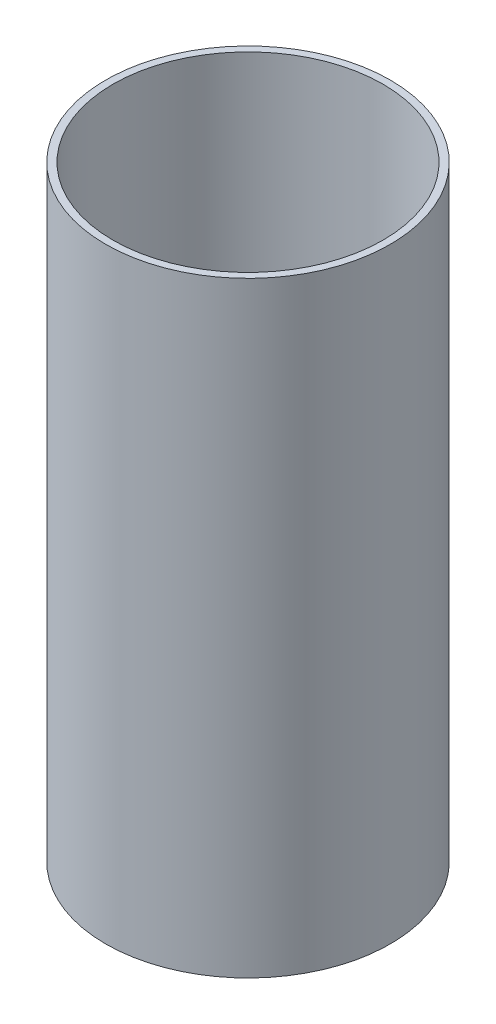
SolidWorks part; units mm, degrees
material "PVC Rigid"
ref_plane "Front Plane" through (0, 0, 0) normal (0, 0, 1) x (1, 0, 0)
ref_plane "Top Plane" through (0, 0, 0) normal (0, 1, 0) x (1, 0, 0)
ref_plane "Right Plane" through (0, 0, 0) normal (1, 0, 0) x (0, 0, -1)
sketch "Sketch1" plane through (0, 0, 0) normal (0, 1, 0) x (1, 0, 0)
  circle A0 centre (0, 0) radius 93.6625
  circle A1 centre (0, 0) radius 88.9
  dimension "D1" = 187.325
  dimension "D2" = 177.8
extrude "Boss-Extrude1" add sketch "Sketch1" along normal mid plane 398.78
ref_plane "Plane1" through (0, 0, 93.6625) normal (0, 0, 1) x (1, 0, 0)
sketch "Sketch3" plane through (0, 0, 93.6625) normal (0, 0, 1) x (1, 0, 0)
  line L0 (0, -103.0288) -> (0, 103.0288) construction
  line L1 (-93.6625, -199.39) -> (93.6625, -199.39) construction
  circle A0 centre (0, -193.04) radius 1.4351
  dimension "D1" = 2.8702
  dimension "D2" = 6.35
extrude "Cut-Extrude1" [suppressed] cut sketch "Sketch3" against normal blind 19.304
pattern_circular "CirPattern1" [suppressed] count 12 over 360 reverse direction yes of bodies 102
mirror "Mirror1" [suppressed] about plane through (0, 0, 0) normal (0, 1, 0)
sketch "Sketch4" [suppressed] plane through (0, 0, 93.6625) normal (0, 0, 1) x (1, 0, 0)
  line L0 (0, -103.0288) -> (0, 103.0288) construction
  circle A0 centre (0, 64.3636) radius 1.4351
  circle A1 centre (0, -64.3636) radius 1.4351
  circle A2 centre (0, 193.04) radius 1.4351 construction
  circle A3 centre (0, -193.04) radius 1.4351 construction
  dimension "D1" = 128.6764
  dimension "D2" = 128.6764
  dimension "D3" = 2.8702
  dimension "D4" = 2.8702
extrude "Cut-Extrude2" [suppressed] cut sketch "Sketch4" against normal blind 43.18
pattern_circular "CirPattern2" [suppressed] count 3 over 360 of bodies 105
